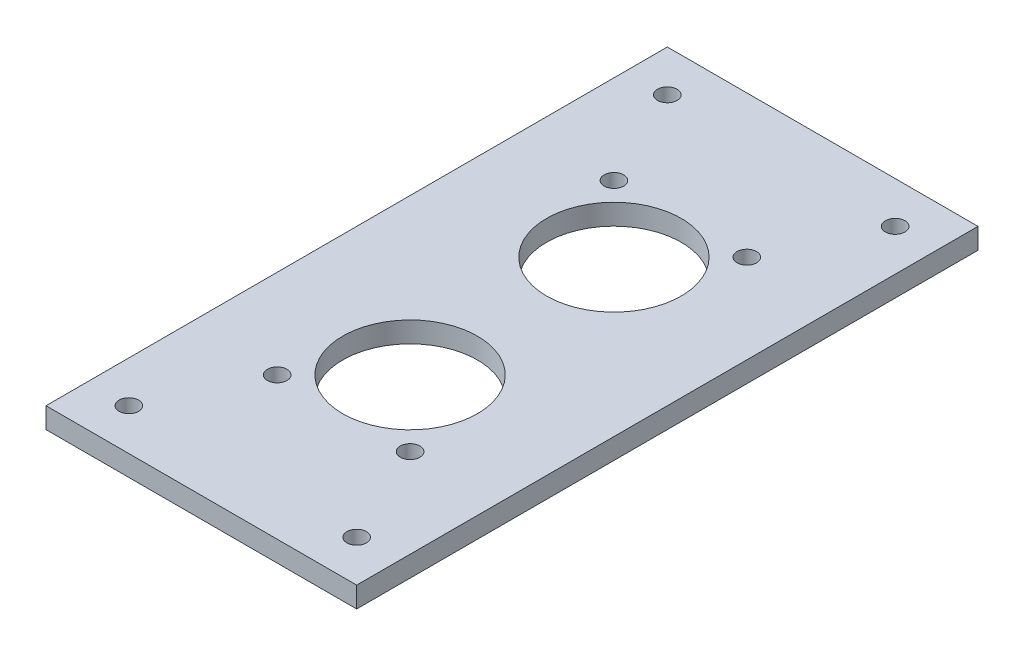
SolidWorks part; units mm, degrees
ref_plane "Front Plane" through (0, 0, 0) normal (0, 0, 1) x (1, 0, 0)
ref_plane "Top Plane" through (0, 0, 0) normal (0, 1, 0) x (1, 0, 0)
ref_plane "Right Plane" through (0, 0, 0) normal (1, 0, 0) x (0, 0, -1)
sketch "Sketch1" plane through (0, 0, 0) normal (0, 1, 0) x (1, 0, 0)
  line L1 (-19.05, -38.1) -> (19.05, -38.1)
  line L2 (-19.05, -38.1) -> (-19.05, 38.1)
  line L3 (-19.05, 38.1) -> (19.05, 38.1)
  line L4 (19.05, -38.1) -> (19.05, 38.1)
  line L5 (-19.05, -38.1) -> (19.05, 38.1) construction
  line L6 (-19.05, 38.1) -> (19.05, -38.1) construction
  point P0 (0, 0)
  dimension "D1" = 76.2
  dimension "D2" = 38.1
extrude "Boss-Extrude1" add sketch "Sketch1" along normal blind 2.54
hole_wizard "#97 (0.65) Diameter Hole1" positions "Sketch2" profile "Sketch3" hole size "#97" standard "ANSI Inch" end condition through all
sketch "Sketch2" plane through (0, 2.54, 0) normal (0, 1, 0) x (1, 0, 0)
  line L0 (0, 12.5006) -> (0, -12.5006) construction
  point P0 (0, -12.5006)
  point P2 (0, 12.5006)
  point P8 (0, 0)
  dimension "D1" = 25.0012
sketch "Sketch3" plane through (0, 2.54, 12.5006) normal (1, 0, 0) x (0, 0, 1)
  line L0 (0, 0) -> (0, 2.54)
  line L1 (0, 2.54) -> (8.255, 2.54)
  line L2 (8.255, 2.54) -> (8.255, 0)
  line L5 (8.255, 0) -> (0, 0)
  line L11 (0, -6.35) -> (0, 107.95) construction
  dimension "Thru Hole Dia." = 16.51
  dimension "Thru Hole Depth" = 2.54
hole_wizard "M2 Clearance Hole2" positions "Sketch5" profile "Sketch6" hole size "M2" standard "ANSI Metric" end condition through all
sketch "Sketch5" plane through (0, 2.54, 0) normal (0, 1, 0) x (1, 0, 0)
  line L1 (-8.1496, -20.6502) -> (8.1496, -20.6502)
  line L2 (-8.1496, -20.6502) -> (-8.1496, 20.6502)
  line L3 (-8.1496, 20.6502) -> (8.1496, 20.6502)
  line L4 (8.1496, -20.6502) -> (8.1496, 20.6502)
  line L5 (-8.1496, -20.6502) -> (8.1496, 20.6502) construction
  line L6 (-8.1496, 20.6502) -> (8.1496, -20.6502) construction
  point P0 (8.1496, 20.6502)
  point P2 (8.1496, -20.6502)
  point P4 (-8.1496, -20.6502)
  point P6 (-8.1496, 20.6502)
  point P52 (0, 0)
  dimension "D1" = 41.3004
  dimension "D2" = 16.2992
sketch "Sketch6" plane through (8.1496, 2.54, -20.6502) normal (1, 0, 0) x (0, 0, 1)
  line L0 (0, 0) -> (0, 2.54)
  line L1 (0, 2.54) -> (1.2, 2.54)
  line L2 (1.2, 2.54) -> (1.2, 0)
  line L5 (1.2, 0) -> (0, 0)
  line L11 (0, -6.35) -> (0, 107.95) construction
  dimension "Thru Hole Dia." = 2.4
  dimension "Thru Hole Depth" = 2.54
hole_wizard "M2 Clearance Hole4" positions "Sketch13" profile "Sketch14" hole size "M2" standard "ANSI Metric" end condition through all
sketch "Sketch13" plane through (0, 2.54, 0) normal (0, 1, 0) x (1, 0, 0)
  line L12 (-16.51, -35.56) -> (16.51, -35.56)
  line L13 (16.51, -35.56) -> (16.51, 35.56)
  line L14 (16.51, 35.56) -> (-16.51, 35.56)
  line L15 (-16.51, 35.56) -> (-16.51, -35.56)
  line L16 (-16.51, -35.56) -> (16.51, -35.56) construction
  line L17 (16.51, -35.56) -> (16.51, 35.56) construction
  line L18 (16.51, 35.56) -> (-16.51, 35.56) construction
  line L19 (-16.51, 35.56) -> (-16.51, -35.56) construction
  line L20 (-13.97, 33.02) -> (-13.97, -33.02) construction
  line L21 (-13.97, -33.02) -> (13.97, -33.02) construction
  line L22 (13.97, -33.02) -> (13.97, 33.02) construction
  line L23 (13.97, 33.02) -> (-13.97, 33.02) construction
  point P0 (-13.97, 33.02)
  point P2 (13.97, 33.02)
  point P34 (-13.97, -33.02)
  point P36 (13.97, -33.02)
  dimension "D1" = 2.54
  dimension "D2" = 2.54
sketch "Sketch14" plane through (-13.97, 2.54, -33.02) normal (1, 0, 0) x (0, 0, 1)
  line L0 (0, 0) -> (0, 2.54)
  line L1 (0, 2.54) -> (1.2, 2.54)
  line L2 (1.2, 2.54) -> (1.2, 0)
  line L5 (1.2, 0) -> (0, 0)
  line L11 (0, -6.35) -> (0, 107.95) construction
  dimension "Thru Hole Dia." = 2.4
  dimension "Thru Hole Depth" = 2.54
